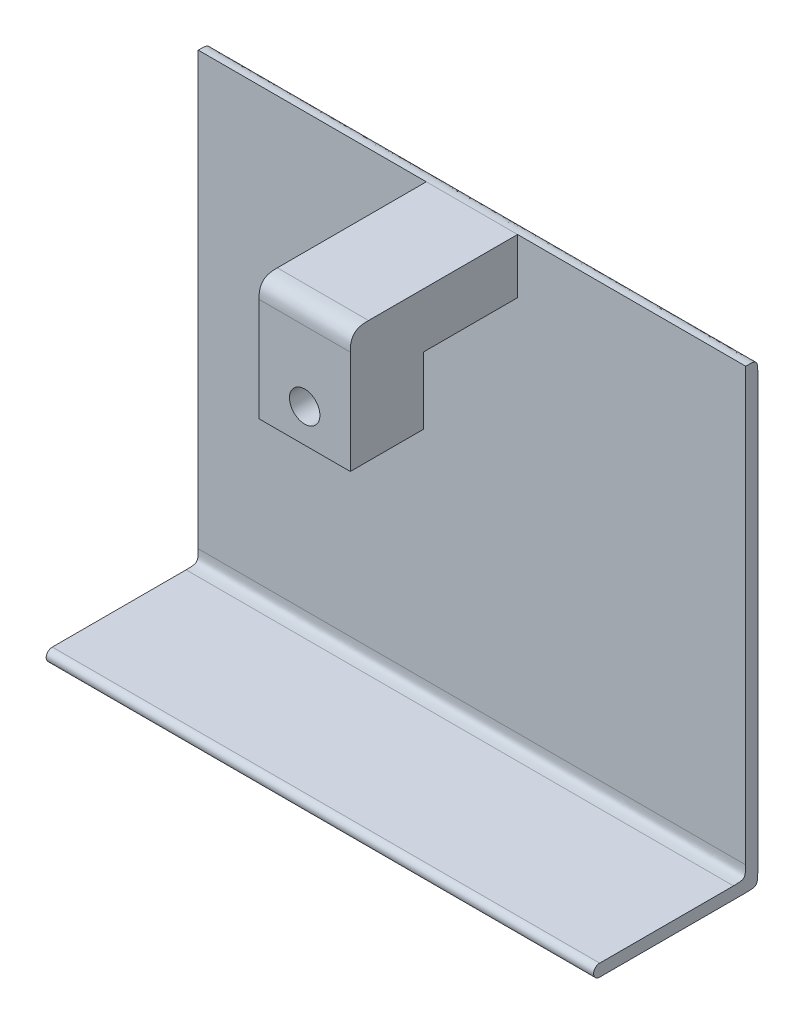
SolidWorks part; units mm, degrees
ref_plane "Front Plane" through (0, 0, 0) normal (0, 0, 1) x (1, 0, 0)
ref_plane "Top Plane" through (0, 0, 0) normal (0, 1, 0) x (1, 0, 0)
ref_plane "Right Plane" through (0, 0, 0) normal (1, 0, 0) x (0, 0, -1)
sketch "Sketch1" plane through (0, 0, 0) normal (0, 1, 0) x (1, 0, 0)
  line L1 (-37.5, -30) -> (37.5, -30)
  line L2 (-37.5, -30) -> (-37.5, 30)
  line L3 (-37.5, 30) -> (37.5, 30)
  line L4 (37.5, -30) -> (37.5, 30)
  line L5 (-37.5, -30) -> (37.5, 30) construction
  line L6 (-37.5, 30) -> (37.5, -30) construction
  point P0 (0, 0)
  dimension "D1" = 75
  dimension "D2" = 60
extrude "Boss-Extrude2" add sketch "Sketch1" along normal blind 100 contours L3 L4 L1 L2
sketch "Sketch2" plane through (0, 0, -30) normal (0, 0, -1) x (-1, 0, 0)
  line L0 (37.5, 100) -> (37.5, 0) construction
  line L1 (-37.5, 100) -> (37.5, 100)
  line L2 (-37.5, 100) -> (-37.5, 55)
  line L3 (-37.5, 55) -> (37.5, 55)
  line L4 (37.5, 100) -> (37.5, 55)
  dimension "D1" = 45
extrude "Boss-Extrude3" add sketch "Sketch2" along normal blind 77.5
sketch "Sketch3" plane through (0, 0, -107.5) normal (0, 0, -1) x (-1, 0, 0)
  line L0 (37.5, 100) -> (-37.5, 100) construction
  line L1 (0, 100) -> (225, 100)
  line L3 (25, -275) -> (225, -275)
  line L4 (225, 100) -> (225, -275)
  line L6 (0, 100) -> (-225, 100)
  line L8 (25, -275) -> (-225, -275)
  line L9 (-225, 100) -> (-225, -275)
  dimension "D1" = 225
  dimension "D2" = 375
  dimension "D3" = 225
extrude "Boss-Extrude4" add sketch "Sketch3" along normal blind 10
sketch "Sketch4" plane through (0, 0, -107.5) normal (0, 0, 1) x (1, 0, 0)
  line L0 (225, 100) -> (225, -275) construction
  line L1 (-225, -275) -> (225, -275)
  line L2 (-225, -275) -> (-225, -265)
  line L3 (-225, -265) -> (225, -265)
  line L4 (225, -275) -> (225, -265)
  dimension "D1" = 10
extrude "Boss-Extrude5" add sketch "Sketch4" along normal blind 125
sketch "Sketch5" plane through (0, 0, 30) normal (0, 0, 1) x (1, 0, 0)
  line L0 (37.5, 0) -> (37.5, 50) construction
  line L1 (37.5, 100) -> (37.5, 0) construction
  line L2 (37.5, 50) -> (37.5, 55.0027) construction
  line L3 (37.5, 55.0027) -> (37.5, 0) construction
  line L4 (37.5, 0) -> (37.5, 25) construction
  line L5 (37.5, 25) -> (37.5, 27.5014) construction
  line L6 (37.5, 27.5014) -> (-37.5, 27.5014) construction
  line L7 (-37.5, 100) -> (-37.5, 0) construction
  line L8 (-37.5, 27.5014) -> (0, 27.5014) construction
  circle A0 centre (0, 27.5014) radius 12.5
extrude "Cut-Extrude1" cut sketch "Sketch5" against normal blind 125
fillet "Fillet3" radius 10 2 edges at (0, -275, -117.5) (0, 100, -117.5) conic rho 0.7
fillet "Fillet4" 2 edges at (0, -265, 17.5) (0, -275, 17.5) type full round first side face at (0, -265, -45) second side face at (-56.25, -275, -76.25) middle face at (0, -270, 17.5)
fillet "Fillet5" radius 10 1 edges at (0, -265, -107.5) conic rho 0.7
fillet "Fillet6" radius 15 1 edges at (0, 100, 30) curvature continuous yes
